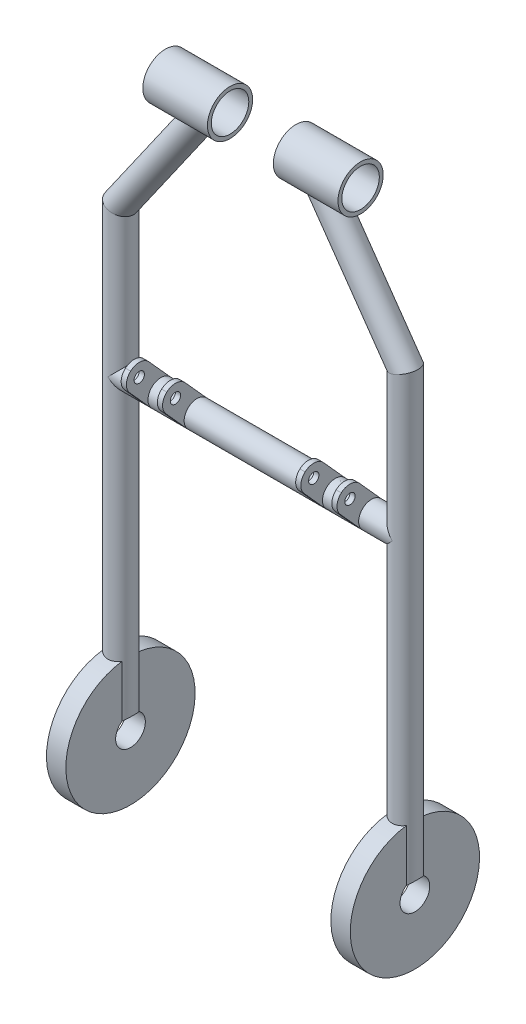
SolidWorks part; units mm, degrees
ref_plane "Alzado" through (0, 0, 0) normal (0, 0, 1) x (1, 0, 0)
ref_plane "Planta" through (0, 0, 0) normal (0, 1, 0) x (1, 0, 0)
ref_plane "Vista lateral" through (0, 0, 0) normal (1, 0, 0) x (0, 0, -1)
sketch "Croquis1" plane through (0, 0, 0) normal (1, 0, 0) x (0, 0, -1)
  circle A0 centre (0, 0) radius 17.5
  circle A1 centre (0, 0) radius 14.5
  dimension "D1" = 35
  dimension "D2" = 3
extrude "Saliente-Extruir1" add sketch "Croquis1" along normal blind 50
sketch "Croquis2" plane through (0, 0, 0) normal (0, 0, 1) x (1, 0, 0)
  line L0 (25, -17.5) -> (-34.5176, -102.5)
  line L1 (-34.5176, -102.5) -> (-34.5176, -452.5)
  line L2 (-34.5176, -102.5) -> (29.5486, -102.5) construction
  line L3 (25, 17.5) -> (25, -17.5) construction
  line L4 (50, 17.5) -> (0, 17.5) construction
  line L5 (0, -17.5) -> (50, -17.5) construction
  line L6 (0, 0) -> (50, 0) construction
  line L7 (50, -17.5) -> (50, 17.5) construction
  dimension "D1" = 85
  dimension "D2" = 350
  dimension "D3" = 55
  dimension "D4" = 64.0663
ref_plane "Plano1" through (25, -17.5, 0) normal (-0.5736, -0.8192, 0) x (0, 0, 1)
sketch "Croquis3" plane through (25, -17.5, 0) normal (-0.5736, -0.8192, 0) x (0, 0, 1)
  circle A0 centre (0, 0) radius 10
  circle A1 centre (0, 0) radius 7
  dimension "D2" = 3
  dimension "D1" = 20
sweep "Barrer1" add profiles "Croquis3" path "Croquis2"
sketch "Croquis4" plane through (50, 0, 0) normal (1, 0, 0) x (0, 0, -1)
  circle A0 centre (0, 0) radius 14.5 construction
  circle A1 centre (0, 0) radius 14.5
extrude "Cortar-Extruir1" cut sketch "Croquis4" against normal through all
sketch "Croquis5" plane through (0.0024, 0.0035, 0) normal (0.5736, 0.8192, 0) x (0.8192, -0.5736, 0)
  arc A4 (40.5164, 0) -> (26.1673, 9.0048) centre (30.5164, 0) ccw
  arc A5 (37.5164, 0) -> (28.2476, 6.6221) centre (30.5164, 0) ccw
  arc A6 (28.2476, -6.6221) -> (37.5164, 0) centre (30.5164, 0) ccw
  arc A7 (26.1673, -9.0048) -> (40.5164, 0) centre (30.5164, 0) ccw
  arc A8 (40.5164, 0) -> (26.1673, 9.0048) centre (30.5164, 0) ccw
  arc A9 (37.5164, 0) -> (28.2476, 6.6221) centre (30.5164, 0) ccw
  arc A10 (28.2476, -6.6221) -> (37.5164, 0) centre (30.5164, 0) ccw
  arc A11 (26.1673, -9.0048) -> (40.5164, 0) centre (30.5164, 0) ccw
  ellipse E2 centre (0.0061, 0) end of major axis (-30.5042, 0) minor radius 17.5 (28.2476, 6.6221) -> (26.1673, 9.0048) ccw
  ellipse E3 centre (0.0061, 0) end of major axis (-30.5042, 0) minor radius 17.5 (26.1673, -9.0048) -> (28.2476, -6.6221) ccw
  ellipse E4 centre (0.0061, 0) end of major axis (-30.5042, 0) minor radius 17.5 (28.2476, 6.6221) -> (26.1673, 9.0048) ccw
  ellipse E5 centre (0.0061, 0) end of major axis (-30.5042, 0) minor radius 17.5 (26.1673, -9.0048) -> (28.2476, -6.6221) ccw
  dimension "D1" = 0
extrude "Saliente-Extruir2" add sketch "Croquis5" along normal up to body separate body
ref_plane "Plano3" through (101, 0, 0) normal (1, 0, 0) x (0, 0, -1)
sketch "Croquis6" plane through (101, 0, 0) normal (1, 0, 0) x (0, 0, -1)
  circle A0 centre (0, 0) radius 14.5 construction
  circle A1 centre (0, 0) radius 17.5 construction
  circle A2 centre (0, 0) radius 14.5
  circle A3 centre (0, 0) radius 17.5
extrude "Saliente-Extruir3" add sketch "Croquis6" along normal blind 50 separate body
sketch "Croquis7" plane through (0, 0, 0) normal (0, 0, 1) x (1, 0, 0)
  line L0 (151, -17.5) -> (151, 17.5) construction
  line L1 (101, -17.5) -> (151, -17.5) construction
  line L2 (101, 17.5) -> (101, -17.5) construction
  line L3 (151, 17.5) -> (101, 17.5) construction
  line L4 (151, -17.5) -> (151, 17.5) construction
  line L5 (101, -17.5) -> (151, -17.5) construction
  line L6 (101, 17.5) -> (101, -17.5) construction
  line L7 (151, 17.5) -> (101, 17.5) construction
  line L8 (126, -17.5) -> (185.5176, -102.5)
  line L9 (185.5176, -102.5) -> (185.5176, -452.5)
  line L10 (185.5176, -102.5) -> (99.3833, -102.5) construction
  dimension "D1" = 85
  dimension "D2" = 350
  dimension "D3" = 86.1343
  dimension "D4" = 55
ref_plane "Plano4" through (126, -17.5, 0) normal (0.5736, -0.8192, 0) x (-0.8192, -0.5736, 0)
sketch "Croquis8" plane through (126, -17.5, 0) normal (0.5736, -0.8192, 0) x (-0.8192, -0.5736, 0)
  circle A0 centre (0, 0) radius 10
  circle A1 centre (0, 0) radius 7
  dimension "D2" = 3
  dimension "D1" = 20
sweep "Barrer2" add profiles "Croquis8" path "Croquis7"
sketch "Croquis9" plane through (49.675, -70.9433, 0) normal (-0.5736, 0.8192, 0) x (0.8192, 0.5736, 0)
  arc A2 (95.4443, 6.6221) -> (95.4443, -6.6221) centre (93.1756, 0) ccw
  arc A3 (97.5246, 9.0048) -> (97.5246, -9.0048) centre (93.1756, 0) ccw
  arc A4 (95.4443, 6.6221) -> (95.4443, -6.6221) centre (93.1756, 0) ccw
  arc A5 (97.5246, 9.0048) -> (97.5246, -9.0048) centre (93.1756, 0) ccw
  ellipse E2 centre (123.6859, 0) end of major axis (93.1756, 0) minor radius 17.5 (97.5246, 9.0048) -> (95.4443, 6.6221) ccw
  ellipse E3 centre (123.6859, 0) end of major axis (93.1756, 0) minor radius 17.5 (95.4443, -6.6221) -> (97.5246, -9.0048) ccw
  ellipse E4 centre (123.6859, 0) end of major axis (93.1756, 0) minor radius 17.5 (97.5246, 9.0048) -> (95.4443, 6.6221) ccw
  ellipse E5 centre (123.6859, 0) end of major axis (93.1756, 0) minor radius 17.5 (95.4443, -6.6221) -> (97.5246, -9.0048) ccw
  dimension "D1" = 0
extrude "Saliente-Extruir4" add sketch "Croquis9" along normal up to surface up to face at (132.5056, -16.5721, 0.0091)
sketch "Croquis10" plane through (0, 0, 0) normal (1, 0, 0) x (0, 0, -1)
  line L0 (10, -102.5) -> (10, -14.3614) construction
  line L1 (-10, -14.3614) -> (-10, -102.5) construction
  line L2 (10, -452.5) -> (10, -102.5) construction
  line L3 (-10, -102.5) -> (-10, -452.5) construction
  line L4 (10, -102.5) -> (10, -14.3614) construction
  line L5 (-10, -14.3614) -> (-10, -102.5) construction
  line L6 (10, -452.5) -> (10, -102.5) construction
  line L7 (-10, -102.5) -> (-10, -452.5) construction
  line L10 (0, -452.5) -> (0, -11.7642) construction
  circle A0 centre (0, -214.3614) radius 10
  dimension "D2" = 20
  dimension "D1" = 200
extrude "Saliente-Extruir5" add sketch "Croquis10" along normal up to surface and the other way up to surface contours A0 up to face at (195.5176, -99.347, 0) other way up to face at (-44.5176, -99.347, 0)
sketch "Croquis11" plane through (0, -452.5, 0) normal (0, -1, 0) x (1, 0, 0)
  line L0 (-34.5176, 0) -> (-44.5176, 0)
  circle A0 centre (-34.5176, 0) radius 10 construction
  circle A1 centre (-34.5176, 0) radius 10 construction
ref_plane "Plano5" through (-34.5176, -452.5, 0) normal (-1, 0, 0) x (0, 0, 1)
sketch "Croquis12" plane through (-34.5176, -452.5, 0) normal (-1, 0, 0) x (0, 0, 1)
  line L0 (-10, 0) -> (10, 0) construction
  circle A0 centre (0, 0) radius 50
  dimension "D1" = 100
extrude "Saliente-Extruir6" add sketch "Croquis12" along normal mid plane 15
chamfer "Chaflán3" distance 7 angle 45 2 edges at (-25.1635, -452.5, -3.5355) (-25.1635, -452.5, 3.5355)
chamfer "Chaflán4" distance 7 angle 45 1 edges at (-44.5176, -452.5, 0)
sketch "Croquis13" plane through (0, -452.5, 0) normal (0, -1, 0) x (1, 0, 0)
  line L0 (185.5176, 0) -> (175.5176, 0) construction
  circle A0 centre (185.5176, 0) radius 10 construction
  circle A1 centre (185.5176, 0) radius 10 construction
ref_plane "Plano6" through (185.5176, -452.5, 0) normal (-1, 0, 0) x (0, 0, 1)
sketch "Croquis14" plane through (185.5176, -452.5, 0) normal (-1, 0, 0) x (0, 0, 1)
  arc A0 (-6.6144, 49.5606) -> (6.6144, 49.5606) centre (0, 0) ccw construction
  arc A1 (-6.6144, 49.5606) -> (6.6144, 49.5606) centre (0, 0) ccw
  circle A2 centre (0, 0) radius 50
extrude "Saliente-Extruir8" add sketch "Croquis14" along normal mid plane 15 contours A2
sketch "Croquis15" plane through (151, 0, 0) normal (1, 0, 0) x (0, 0, -1)
  circle A0 centre (0, 0) radius 14.5 construction
  circle A1 centre (0, 0) radius 14.5
extrude "Cortar-Extruir2" cut sketch "Croquis15" against normal through all contours A1
ref_plane "Plano7" through (75, 0, 0) normal (1, 0, 0) x (0, 0, -1)
sketch "Croquis16" plane through (75, 0, 0) normal (1, 0, 0) x (0, 0, -1)
  line L0 (0, -214.3614) -> (-23.4196, -188.3513)
  line L1 (0, -214.3614) -> (0, -164.3614) construction
  arc A0 (-10, -214.3614) -> (10, -214.3614) centre (0, -214.3614) ccw construction
  arc A1 (10, -214.3614) -> (-10, -214.3614) centre (0, -214.3614) ccw construction
  arc A2 (-10, -214.3614) -> (10, -214.3614) centre (0, -214.3614) ccw
  arc A3 (10, -214.3614) -> (-10, -214.3614) centre (0, -214.3614) ccw
  dimension "D1" = 50
  dimension "D2" = 42
  dimension "D3" = 35
ref_plane "Plano8" through (75, -188.3513, 23.4196) normal (0, 0.7431, 0.6691) x (1, 0, 0)
sketch "Croquis17" plane through (75, -188.3513, 23.4196) normal (0, 0.7431, 0.6691) x (1, 0, 0)
  line L0 (120.5176, -159.3458) -> (120.5176, 76.9597) construction
  line L1 (-119.5176, 76.9597) -> (-119.5176, -154.6619) construction
  line L2 (120.5176, -159.3458) -> (120.5176, 76.9597) construction
  line L3 (-119.5176, 76.9597) -> (-119.5176, -154.6619) construction
  line L4 (-102.8263, -10) -> (103.8263, -10) construction
  line L5 (103.8263, 10) -> (-102.8263, 10) construction
  line L6 (-102.8263, -10) -> (103.8263, -10) construction
  line L7 (103.8263, 10) -> (-102.8263, 10) construction
  line L8 (-119.5176, 0) -> (120.5176, 0) construction
  line L9 (-82.5, 10) -> (-78.5, 10)
  line L10 (-82.5, 10) -> (-82.5, -10)
  line L11 (-82.5, -10) -> (-78.5, -10)
  line L12 (-78.5, 10) -> (-78.5, -10)
  line L13 (-82.5, 10) -> (-78.5, -10) construction
  line L14 (-82.5, -10) -> (-78.5, 10) construction
  line L15 (-50.5, 10) -> (-54.5, 10)
  line L16 (-50.5, 10) -> (-50.5, -10)
  line L17 (-50.5, -10) -> (-54.5, -10)
  line L18 (-54.5, 10) -> (-54.5, -10)
  line L19 (-50.5, 10) -> (-54.5, -10) construction
  line L20 (-50.5, -10) -> (-54.5, 10) construction
  line L29 (0, 0) -> (0, 33.4565) construction
  line L30 (0.5, 0) -> (0.5, -10) construction
  line L31 (0, 0) -> (0, 33.4565) construction
  line L32 (52.5, -10) -> (56.5, -10)
  line L33 (52.5, 10) -> (52.5, -10)
  line L34 (52.5, 10) -> (56.5, 10)
  line L35 (56.5, 10) -> (56.5, -10)
  line L36 (84.5, -10) -> (80.5, -10)
  line L37 (80.5, 10) -> (80.5, -10)
  line L38 (84.5, 10) -> (80.5, 10)
  line L39 (84.5, 10) -> (84.5, -10)
  point P12 (-80.5, 0)
  point P17 (-52.5, 0)
  dimension "D1" = 24
  dimension "D2" = 4
  dimension "D3" = 4
  dimension "D4" = 50.5
  dimension "D5" = 52.5
  dimension "D6" = 24
  dimension "D7" = 4
  dimension "D8" = 4
extrude "Saliente-Extruir10" add sketch "Croquis17" against normal up to body separate body contours L12 L11 L10 L9 | L16 L17 L18 L15 | L35 L34 L33 L32 | L36 L37 L38 L39
fillet "Redondeo1" radius 10 8 edges at (157.5, -195.0426, 30.851) (157.5, -181.66, 15.9881) (129.5, -195.0426, 30.851) (129.5, -181.66, 15.9881) (-5.5, -195.0426, 30.851) (-5.5, -181.66, 15.9881) (22.5, -181.66, 15.9881) (22.5, -195.0426, 30.851)
sketch "Croquis18" plane through (-7.5, 0, 0) normal (-1, 0, 0) x (0, 0, 1)
  circle A0 centre (16.7283, -195.7828) radius 4
  dimension "D1" = 8
extrude "Cortar-Extruir3" cut sketch "Croquis18" against normal through all
ref_plane "Plano9" through (-52.0176, 0, 0) normal (-1, 0, 0) x (0, 0, 1)
sketch "Croquis19" plane through (-52.0176, 0, 0) normal (-1, 0, 0) x (0, 0, 1)
  line L0 (-10, -452.5) -> (10, -452.5) construction
  circle A0 centre (0, -452.5) radius 50 construction
  arc A1 (-6.6144, -402.9394) -> (6.6144, -402.9394) centre (0, -452.5) ccw construction
  circle A2 centre (0, -452.5) radius 11.5
  dimension "D1" = 23
extrude "Cortar-Extruir4" cut sketch "Croquis19" against normal through all contours A2
equation "\"Diam_Tubo\"=35"
equation "\"D1@Croquis1\"=\"Diam_Tubo\""
equation "\"Grosor_Tubo\"=3"
equation "\"D2@Croquis1\"=\"Grosor_Tubo\""
equation "\"Dist_Sec\"=85"
equation "\"D1@Croquis2\"=\"Dist_Sec\""
equation "\"Diste_sec\" = 350"
equation "\"D2@Croquis2\"=\"Diste_sec\""
equation "\"Inclinacion_Princ\"= 55"
equation "\"D3@Croquis2\"=\"Inclinacion_Princ\""
equation "\"D2@Croquis3\"=\"Grosor_Tubo\""
equation "\"Diam_Tubo2\"=20"
equation "\"D1@Croquis3\"=\"Diam_Tubo2\""
equation "\"Ext_Tubo\"= 50"
equation "\"D1@Saliente-Extruir1\"=\"Ext_Tubo\""
equation "\"D1@Saliente-Extruir3\"=\"Ext_Tubo\""
equation "\"D1@Croquis7\"=\"Dist_Sec\""
equation "\"D2@Croquis7\"=\"Diste_sec\""
equation "\"D4@Croquis7\"=\"Inclinacion_Princ\""
equation "\"D1@Croquis8\"=\"Diam_Tubo2\""
equation "\"D2@Croquis8\"=\"Grosor_Tubo\""
equation "\"Dist_Soporte_Amortiguador\" = 200"
equation "\"D2@Croquis10\"=\"Diam_Tubo2\""
equation "\"Ext_Sop_Rueda\"= 15"
equation "\"D1@Saliente-Extruir6\"=\"Ext_Sop_Rueda\""
equation "\"Tubo_Rueda\"= 100"
equation "\"D1@Saliente-Extruir8\"=\"Ext_Sop_Rueda\""
equation "\"Ang_Perp_SopAmort\"= 42"
equation "\"D2@Croquis16\"=\"Ang_Perp_SopAmort\""
equation "\"Largo_SopAmort\"= 35"
equation "\"D3@Croquis16\"=\"Largo_SopAmort\""
equation "\"Dist_Entre_SopAmort\"= 24"
equation "\"D1@Croquis17\"=\"Dist_Entre_SopAmort\""
equation "\"Grosor_SopAmort\"=4"
equation "\"D2@Croquis17\"=\"Grosor_SopAmort\""
equation "\"D3@Croquis17\"=\"Grosor_SopAmort\""
equation "\"Dist_SopRu_SopAmort\"=36.881"
equation "\"Agujero_Amort\"=8"
equation "\"D1@Croquis10\"=\"Dist_Soporte_Amortiguador\""
equation "\"D1@Croquis12\"=\"Tubo_Rueda\""
equation "\"D1@Croquis18\"=\"Agujero_Amort\""
equation "\"D6@Croquis17\"=\"D1@Croquis17\""
equation "\"D7@Croquis17\"=\"D3@Croquis17\""
equation "\"D8@Croquis17\"=\"D3@Croquis17\""
equation "\"Entrada_Eje\"=23"
equation "\"D1@Croquis19\"=\"Entrada_Eje\""
